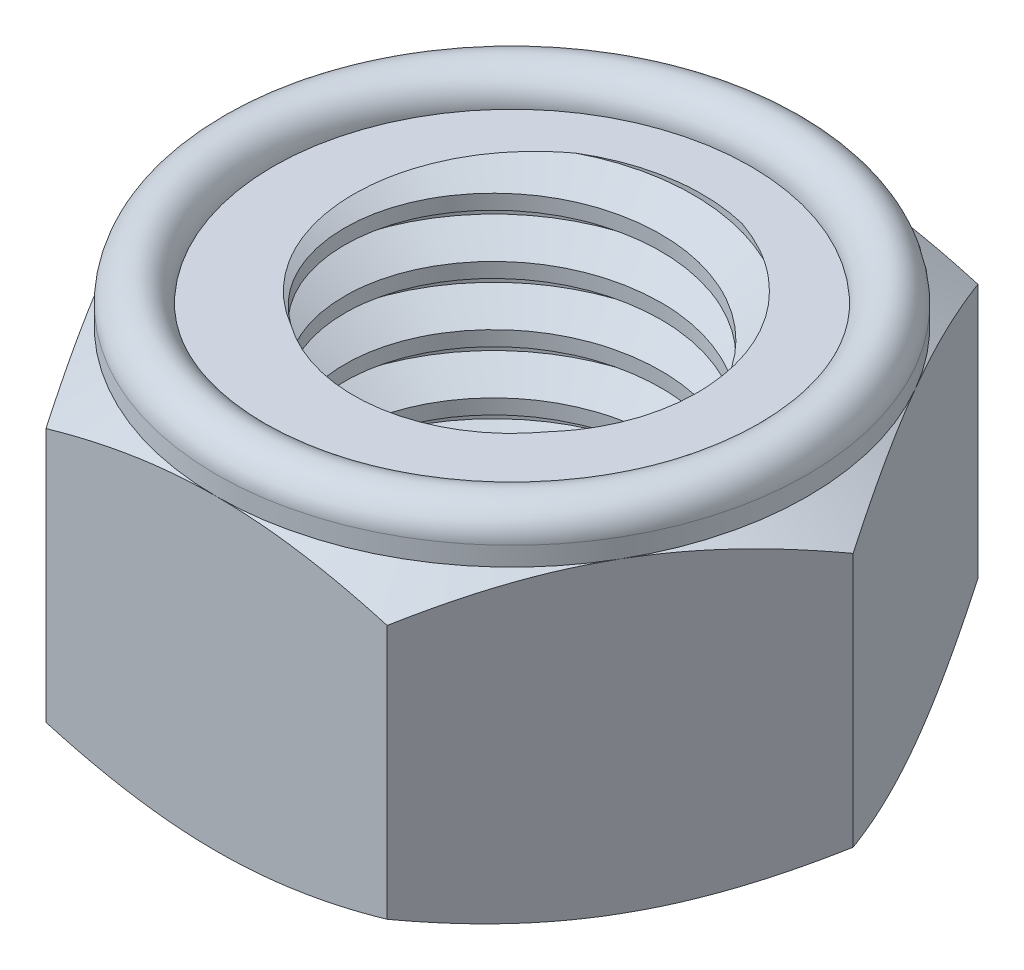
SolidWorks part; units mm, degrees
material "Plain Carbon Steel"
ref_plane "Front Plane" through (0, 0, 0) normal (0, 0, 1) x (1, 0, 0)
ref_plane "Top Plane" through (0, 0, 0) normal (0, 1, 0) x (1, 0, 0)
ref_plane "Right Plane" through (0, 0, 0) normal (1, 0, 0) x (0, 0, -1)
sketch "Sketch1" plane through (0, 0, 0) normal (0, 1, 0) x (1, 0, 0)
  line L1 (-9.1654, 0) -> (-4.5827, -7.9375)
  line L2 (-4.5827, -7.9375) -> (4.5827, -7.9375)
  line L3 (4.5827, -7.9375) -> (9.1654, 0)
  line L4 (9.1654, 0) -> (4.5827, 7.9375)
  line L5 (4.5827, 7.9375) -> (-4.5827, 7.9375)
  line L6 (-4.5827, 7.9375) -> (-9.1654, 0)
  circle A0 centre (0, 0) radius 7.9375 construction
  dimension "D1" = 15.875
extrude "Boss-Extrude1" add sketch "Sketch1" along normal blind 9.525
sketch "Sketch2" plane through (0, 0, 0) normal (0, 0, 1) x (1, 0, 0)
  line L0 (-9.1654, 0.7089) -> (-7.9375, 0)
  line L1 (-9.1654, 9.525) -> (-9.1654, 0) construction
  line L2 (-9.1654, 0) -> (-4.5827, 0) construction
  line L3 (-7.9375, 0) -> (-9.1654, 0)
  line L4 (-9.1654, 0) -> (-9.1654, 0.7089)
  line L5 (-9.1654, 7.5461) -> (-7.9375, 8.255)
  line L6 (-7.9375, 8.255) -> (-7.9375, 8.763)
  line L7 (-6.4135, 8.763) -> (-4.2545, 8.763)
  line L8 (-4.2545, 8.763) -> (-4.2545, 0)
  line L9 (-4.2545, 0) -> (0, 0)
  line L10 (0, 0) -> (0, 9.525)
  line L11 (-4.5827, 9.525) -> (4.5827, 9.525) construction
  line L12 (0, 9.525) -> (-9.1654, 9.525)
  line L13 (-9.1654, 9.525) -> (-9.1654, 7.5461)
  arc A0 (-7.9375, 8.763) -> (-6.4135, 8.763) centre (-7.1755, 8.763) cw
  dimension "D6" = 0.762
  dimension "D1" = 30
  dimension "D2" = 7.9375
  dimension "D3" = 30
  dimension "D4" = 1.27
  dimension "D5" = 4.2545
revolve "Cut-Revolve1" cut sketch "Sketch2" angle 360 about L10 region at (-8.7561, 0.2363, 0) region at (-8.5474, 8.7384, 0) region at (-2.2651, 4.9465, 0)
sketch "Sketch6" plane through (0, 0, 0) normal (0, 0, 1) x (1, 0, 0)
  line L0 (-4.2545, 6.985) -> (-4.2545, 6.731)
  line L1 (-4.2545, 6.731) -> (-4.3815, 6.858)
  line L2 (-4.3815, 6.858) -> (-4.2545, 6.985)
  line L3 (0, 0) -> (0, 7.8361) construction
  line L6 (-4.2545, 8.763) -> (-4.2545, 6.985) construction
  dimension "D1" = 0.254
  dimension "D2" = 1.778
revolve "Cut-Revolve2" [suppressed] cut sketch "Sketch6" angle 360 about L3
thread "Thread1" pitch 1.5875 method cut profile "Thread Profile1" start angle 0, offset 2.54, length 15.24, pitch 1.5875, diameter 8.509
ref_plane "Plane1" through (-4.2545, 11.303, 0) normal (0, 0, 1) x (-1, 0, 0)
sketch "Thread Profile1" plane through (-4.2545, 11.303, 0) normal (0, 0, 1) x (-1, 0, 0)
  line L0 (0, 0) -> (0, 1.5875) construction
  line L1 (0, 0) -> (0.8593, 0.4961)
  line L2 (0.8593, 0.4961) -> (0.8593, 0.6945)
  line L3 (0.8593, 0.6945) -> (0, 1.1906)
  line L4 (0.8593, 0.5953) -> (0, 0.5953) construction
  line L11 (0, 0) -> (0, 1.1906)
  point P2 (0, 0)
  dimension "Pitch" = 1.5875
  dimension "Profile_Angle" = 60
  dimension "Profile_Land" = 0.1984
  dimension "Profile_Height" = 0.8593
